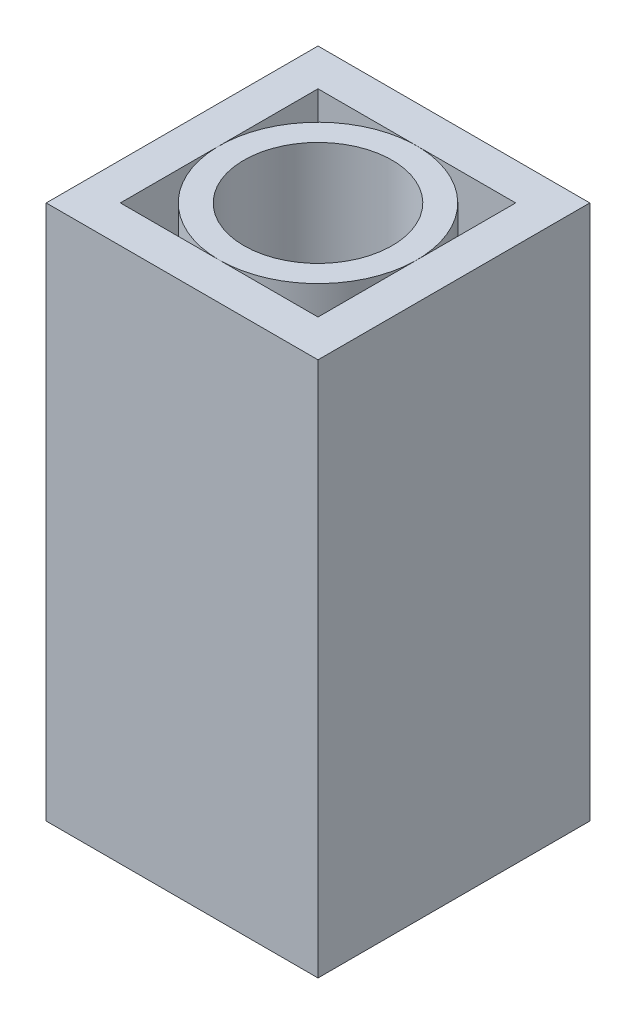
SolidWorks part; units mm, degrees
ref_plane "前视基准面" through (0, 0, 0) normal (0, 0, 1) x (1, 0, 0)
ref_plane "上视基准面" through (0, 0, 0) normal (0, 1, 0) x (1, 0, 0)
ref_plane "右视基准面" through (0, 0, 0) normal (1, 0, 0) x (0, 0, -1)
sketch "草图1" plane through (0, 0, 0) normal (0, 1, 0) x (1, 0, 0)
  line L0 (0, 12) -> (-12, 12)
  line L1 (-16.5, -16.5) -> (16.5, -16.5)
  line L2 (-16.5, -16.5) -> (-16.5, 16.5)
  line L3 (-16.5, 16.5) -> (16.5, 16.5)
  line L4 (16.5, -16.5) -> (16.5, 16.5)
  line L5 (-12, 12) -> (-12, -12)
  line L6 (-12, -12) -> (12, -12)
  line L7 (12, -12) -> (12, 12)
  line L8 (12, 12) -> (0, 12)
  circle A0 centre (0, 0) radius 9
  circle A1 centre (0, 0) radius 12
  dimension "D1" = 18
  dimension "D2" = 24
extrude "凸台-拉伸1" add sketch "草图1" along normal blind 65 contours L1 L4 L3 L2 L8 L7 L6 L5 L0 | A1 A0 region at (8.2453, 0, -8.2453) region at (-16.0333, 0, 0)
extrude "凸台-拉伸2" add sketch "草图1<3>" along normal blind 30 contours A0 region at (0, 0, 0)
sketch "草图1<3>" plane through (0, 0, 0) normal (0, 1, 0) x (1, 0, 0) same geometry as "草图1"
